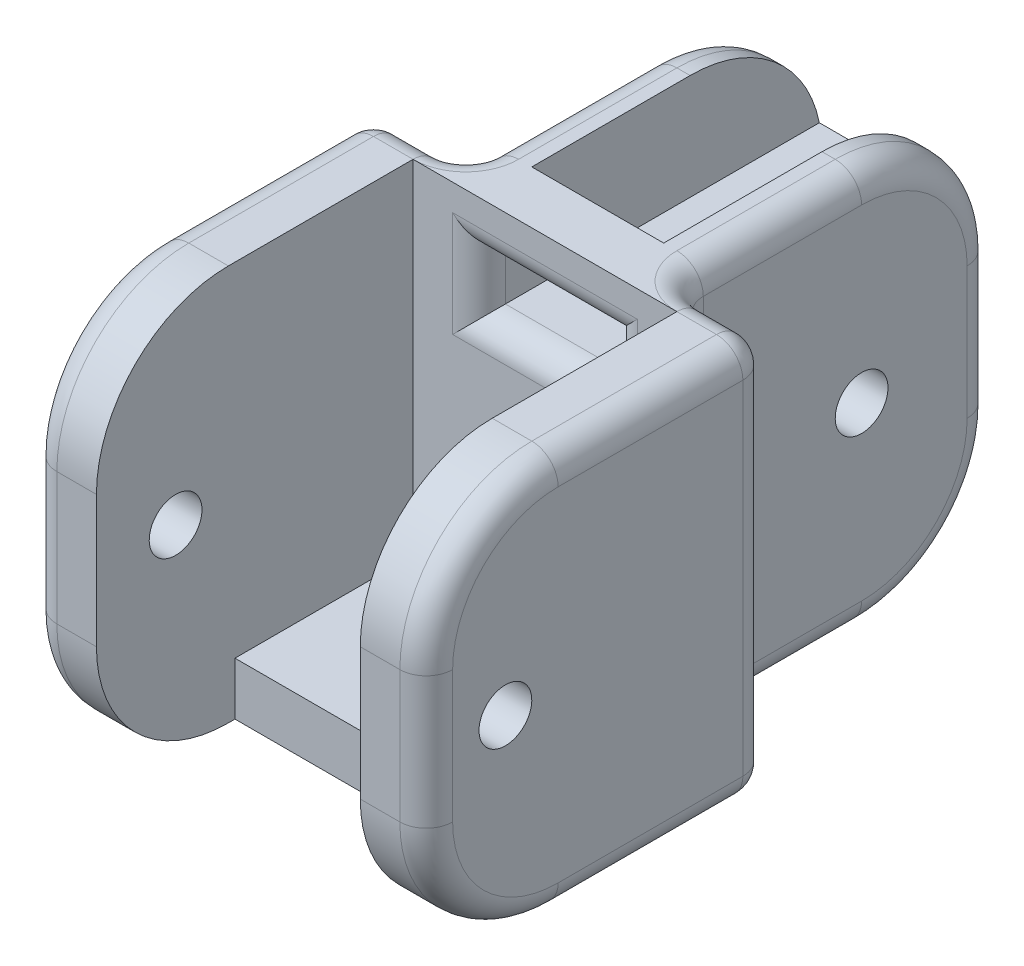
SolidWorks part; units mm, degrees
ref_plane "Front Plane" through (0, 0, 0) normal (0, 0, 1) x (1, 0, 0)
ref_plane "Top Plane" through (0, 0, 0) normal (0, 1, 0) x (1, 0, 0)
ref_plane "Right Plane" through (0, 0, 0) normal (1, 0, 0) x (0, 0, -1)
sketch "Base Sketch" plane through (0, 0, 0) normal (0, 0, 1) x (1, 0, 0)
  line L1 (-7.5, 7.5) -> (7.5, 7.5)
  line L2 (-7.5, 7.5) -> (-7.5, -7.5)
  line L3 (-7.5, -7.5) -> (7.5, -7.5)
  line L4 (7.5, 7.5) -> (7.5, -7.5)
  line L5 (-7.5, 7.5) -> (7.5, -7.5) construction
  line L6 (-7.5, -7.5) -> (7.5, 7.5) construction
  point P0 (0, 0)
  dimension "D1" = 15
  dimension "D2" = 15
extrude "Base Sketch Extrude" add sketch "Base Sketch" along normal blind 25
sketch "Center Nub Cutout Sketch" plane through (0, 0, 0) normal (0, 0, 1) x (1, 0, 0)
  line L0 (0, 0) -> (0, 10.3723) construction
  line L1 (-7.5, -7.5) -> (7.5, -7.5) construction
  line L2 (7.5, 7.5) -> (4, 7.5)
  line L3 (7.5, 7.5) -> (7.5, -7.5)
  line L4 (7.5, -7.5) -> (4, -7.5)
  line L5 (4, 7.5) -> (4, -7.5)
  line L6 (-7.5, -7.5) -> (-4, -7.5)
  line L7 (-4, 7.5) -> (-4, -7.5)
  line L8 (-7.5, 7.5) -> (-4, 7.5)
  line L9 (-7.5, 7.5) -> (-7.5, -7.5)
  dimension "D1" = 4
extrude "Hinge Nub Extruded Cut" cut sketch "Center Nub Cutout Sketch" along normal blind 12
sketch "Hinge Cutout Sketch" plane through (0, 0, 25) normal (0, 0, 1) x (1, 0, 0)
  line L0 (0, 0) -> (0, 10.344) construction
  line L1 (7.5, 7.5) -> (-7.5, 7.5) construction
  line L2 (-5, 7.5) -> (5, 7.5)
  line L3 (-5, 7.5) -> (-5, -7.5)
  line L4 (-5, -7.5) -> (5, -7.5)
  line L5 (5, 7.5) -> (5, -7.5)
  line L6 (-7.5, -7.5) -> (7.5, -7.5) construction
  dimension "D1" = 10
extrude "Hinge Cutout Extruded Cut" cut sketch "Hinge Cutout Sketch" against normal blind 12
sketch "Hinge Hole Sketch" plane through (7.5, 0, 0) normal (1, 0, 0) x (0, 0, -1)
  line L0 (0, 0) -> (-25, 0) construction
  line L1 (-25, -7.5) -> (-25, 7.5) construction
  line L2 (0, 7.5) -> (0, -7.5) construction
  circle A0 centre (-5, 0) radius 1
  circle A1 centre (-22, 0) radius 1
  dimension "D1" = 2
  dimension "D2" = 3
  dimension "D3" = 5
extrude "Hinge Hole Extruded Cut" cut sketch "Hinge Hole Sketch" against normal through all
fillet "Corner Fillets" radius 5 6 edges at (-6.25, -7.5, 25) (-6.25, 7.5, 25) (6.25, -7.5, 25) (6.25, 7.5, 25) (0, -7.5, 0) (0, 7.5, 0)
fillet "Style Fillets" radius 1 28 edges at (-7.5, -7.5, 16) (-7.5, -6.0355, 23.5355) (-7.5, 0, 25) (-7.5, 6.0355, 23.5355) (7.5, -7.5, 16) (7.5, -6.0355, 23.5355) (7.5, 0, 25) (7.5, 6.0355, 23.5355) (-4, -7.5, 8.5) (-4, -6.0355, 1.4645) (-4, 0, 0) (-4, 6.0355, 1.4645) (4, -7.5, 8.5) (4, -6.0355, 1.4645) (4, 0, 0) (4, 6.0355, 1.4645) (5.75, -7.5, 12) (7.5, 0, 12) (5.75, 7.5, 12) (-7.5, 0, 12) (-5.75, -7.5, 12) (-5.75, 7.5, 12) (-7.5, 7.5, 16) (7.5, 7.5, 16) (-4, 7.5, 8.5) (4, 7.5, 8.5) (-4, 0, 12) (4, 0, 12)
sketch "Routing Holes Sketch" plane through (0, 0, 0) normal (0, 0, 1) x (1, 0, 0)
  line L0 (0, 0) -> (12.4478, 0) construction
  line L1 (0, 0) -> (0, 10.921) construction
  line L2 (5, 7.5) -> (-5, 7.5) construction
  line L3 (-2.5, 5.5) -> (2.5, 5.5)
  line L4 (-2.5, 5.5) -> (-2.5, 3.5)
  line L5 (-2.5, 3.5) -> (2.5, 3.5)
  line L6 (2.5, 5.5) -> (2.5, 3.5)
  line L7 (2.5, -5.5) -> (2.5, -3.5)
  line L8 (-2.5, -3.5) -> (2.5, -3.5)
  line L9 (-2.5, -5.5) -> (-2.5, -3.5)
  line L10 (-2.5, -5.5) -> (2.5, -5.5)
  dimension "D1" = 5
  dimension "D2" = 2
  dimension "D3" = 2
extrude "Routing Holes Extruded Cut" cut sketch "Routing Holes Sketch" along normal through all
sketch "Sketch1" plane through (0, 0, 13) normal (0, 0, 1) x (1, 0, 0)
  line L0 (5, -7.5) -> (5, 7.5) construction
  line L1 (-5, -7.5) -> (5, -7.5)
  line L2 (-5, -7.5) -> (-5, -5.5)
  line L3 (-5, -5.5) -> (5, -5.5)
  line L4 (5, -7.5) -> (5, -5.5)
  line L5 (2.5, -5.5) -> (-2.5, -5.5) construction
extrude "Backing Extrude" add sketch "Sketch1" along normal blind 6.75
sketch "Extra Routing Cut Sketch" plane through (0, 7.5, 0) normal (0, 1, 0) x (1, 0, 0)
  line L1 (-2.5, -1) -> (2.5, -1)
  line L2 (-2.5, -1) -> (-2.5, -11)
  line L3 (-2.5, -11) -> (2.5, -11)
  line L4 (2.5, -1) -> (2.5, -11)
  dimension "D1" = 10
extrude "Extra Routing Extruded Cut" cut sketch "Extra Routing Cut Sketch" against normal up to surface (4 mm away) up to face at (0, 3.5, 6.5505)
fillet "Routing Fillets" radius 1 9 edges at (0, -3.5, 0.101) (2.5, -4.5, 13) (0, -3.5, 13) (-2.5, -4.5, 13) (2.5, 4.5, 13) (0, 3.5, 13) (-2.5, 4.5, 13) (0, 5.5, 13) (0, 5.5, 11)
